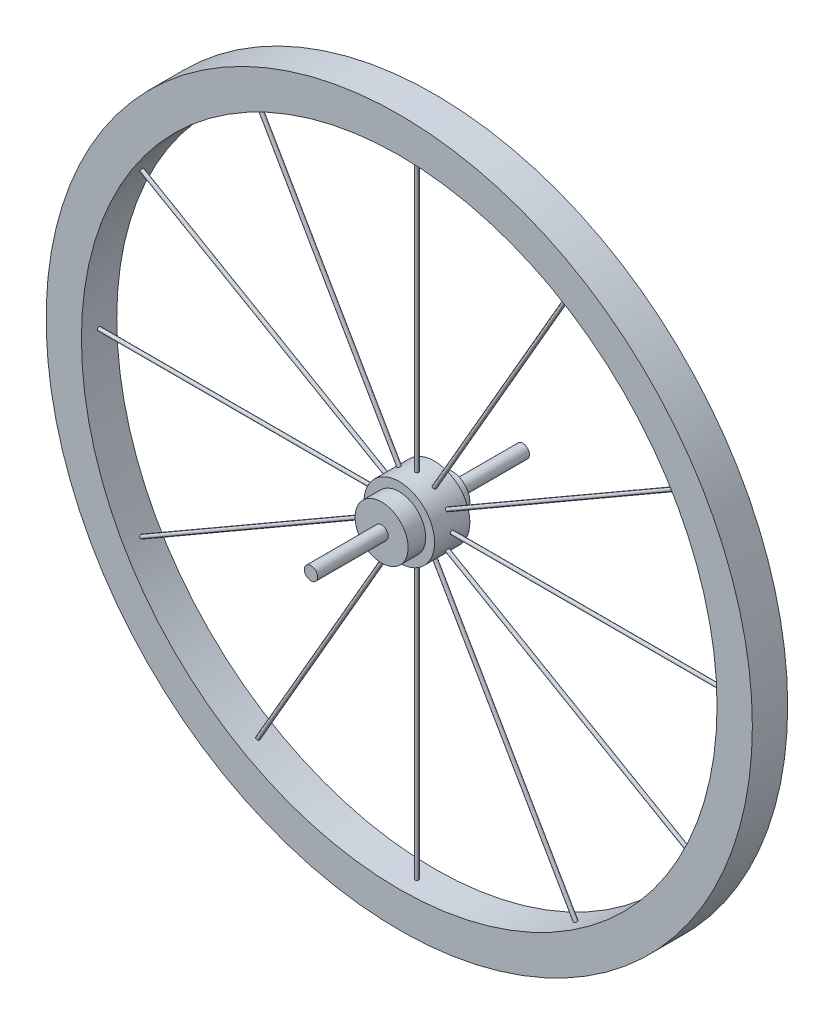
SolidWorks part; units mm, degrees
ref_plane "Front Plane" through (0, 0, 0) normal (0, 0, 1) x (1, 0, 0)
ref_plane "Top Plane" through (0, 0, 0) normal (0, 1, 0) x (1, 0, 0)
ref_plane "Right Plane" through (0, 0, 0) normal (1, 0, 0) x (0, 0, -1)
sketch "Sketch1" plane through (0, 0, 0) normal (0, 0, 1) x (1, 0, 0)
  circle A0 centre (0, 0) radius 25.4
  dimension "D1" = 50.8
extrude "Boss-Extrude1" add sketch "Sketch1" along normal blind 12.7 and the other way blind 12.7
sketch "Sketch2" plane through (0, 0, 0) normal (0, 0, 1) x (1, 0, 0)
  line L0 (0, 0) -> (228.6, 0)
sweep "Sweep1" add path "Sketch2" circular profile diameter 2.54 parameters "D3"=2.54
pattern_circular "CirPattern1" count 12 over 360 about axis through (0, 0, 12.7) along (0, 0, 1) of "Sweep1"
sketch "Sketch43" plane through (0, 0, 0) normal (0, 0, 1) x (1, 0, 0)
  circle A0 centre (0, 0) radius 228.6
  circle A1 centre (0, 0) radius 254
extrude "Boss-Extrude2" add sketch "Sketch43" along normal blind 12.7 and the other way blind 12.7
ref_plane "Plane1" through (0, 0, 12.7) normal (0, 0, 1) x (1, 0, 0)
sketch "Sketch44" plane through (0, 0, 12.7) normal (0, 0, 1) x (1, 0, 0)
  circle A0 centre (0, 0) radius 19.05
extrude "Boss-Extrude3" add sketch "Sketch44" along normal blind 12.7 contours A0
ref_plane "Plane2" through (0, 0, -12.7) normal (0, 0, 1) x (1, 0, 0)
sketch "Sketch46" plane through (0, 0, -12.7) normal (0, 0, -1) x (-1, 0, 0)
  circle A0 centre (0, 0) radius 12.7
extrude "Boss-Extrude4" add sketch "Sketch46" along normal blind 12.7
sketch "Sketch47" plane through (0, 0, 0) normal (0, 0, 1) x (1, 0, 0)
  circle A0 centre (0, 0) radius 4.7625
extrude "Boss-Extrude5" add sketch "Sketch47" along normal blind 76.2 and the other way blind 76.2
